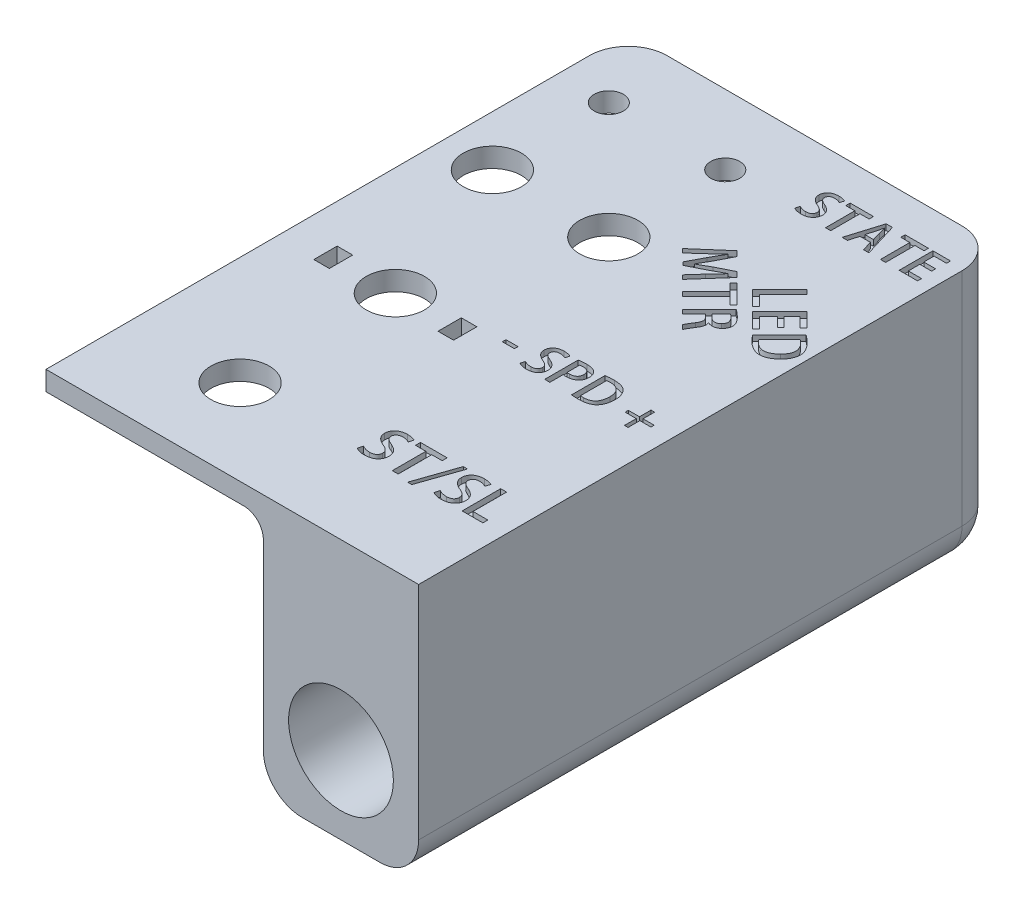
SolidWorks part; units mm, degrees
ref_plane "Front Plane" through (0, 0, 0) normal (0, 0, 1) x (1, 0, 0)
ref_plane "Top Plane" through (0, 0, 0) normal (0, 1, 0) x (1, 0, 0)
ref_plane "Right Plane" through (0, 0, 0) normal (1, 0, 0) x (0, 0, -1)
sketch "Sketch1" plane through (0, 0, 0) normal (0, 1, 0) x (1, 0, 0)
  line L0 (28, 75) -> (28, 0) construction
  line L1 (0, 0) -> (48, 0)
  line L2 (0, 0) -> (0, 70)
  line L3 (5, 75) -> (43, 75)
  line L4 (48, 0) -> (48, 70)
  line L5 (6.5, 51) -> (21.5, 51) construction
  line L6 (5, 32.5) -> (7, 32.5)
  line L7 (5, 32.5) -> (5, 29.5)
  line L8 (5, 29.5) -> (7, 29.5)
  line L9 (7, 32.5) -> (7, 29.5)
  line L10 (23, 32.5) -> (21, 32.5)
  line L11 (23, 32.5) -> (23, 29.5)
  line L12 (23, 29.5) -> (21, 29.5)
  line L13 (21, 32.5) -> (21, 29.5)
  line L14 (6.5, 66) -> (21.5, 66) construction
  circle A0 centre (14, 11) radius 3.75
  circle A1 centre (14, 31) radius 3.75
  circle A2 centre (6.5, 51) radius 3.75
  circle A3 centre (21.5, 51) radius 3.75
  circle A4 centre (6.5, 66) radius 1.875
  circle A5 centre (21.5, 66) radius 1.875
  arc A6 (48, 70) -> (43, 75) centre (43, 70) ccw
  arc A7 (5, 75) -> (0, 70) centre (5, 70) ccw
  point P27 (6, 32.5)
  point P28 (22, 32.5)
  point P29 (21, 31)
  point P30 (5, 31)
  point P31 (14, 51)
  point P32 (0, 0)
  point P33 (14, 66)
  point P36 (48, 75)
  point P39 (0, 75)
  dimension "D4" = 7.5
  dimension "D8" = 20
  dimension "D15" = 5
  dimension "D16" = 3.75
  dimension "D1" = 75
  dimension "D2" = 48
  dimension "D3" = 20
  dimension "D5" = 11
  dimension "D6" = 20
  dimension "D7" = 14
  dimension "D9" = 8
  dimension "D10" = 8
  dimension "D11" = 2
  dimension "D12" = 3
  dimension "D13" = 15
  dimension "D14" = 15
extrude "Boss-Extrude1" add sketch "Sketch1" along normal blind 2.5
sketch "Sketch2" plane through (0, 0, 0) normal (0, -1, 0) x (1, 0, 0)
  line L0 (43, -75) -> (5, -75) construction
  line L1 (48, 0) -> (28, 0)
  line L2 (48, 0) -> (48, -70)
  line L3 (43, -75) -> (28, -75)
  line L4 (28, 0) -> (28, -75)
  arc A0 (48, -70) -> (43, -75) centre (43, -70) cw
  dimension "D2" = 5
  dimension "D1" = 20
extrude "Boss-Extrude2" add sketch "Sketch2" along normal blind 31
sketch "Sketch3" plane through (0, 0, 0) normal (0, 0, 1) x (1, 0, 0)
  line L0 (28, -11) -> (48, -11) construction
  line L1 (28, -31) -> (28, 0) construction
  line L2 (48, 2.5) -> (48, -31) construction
  line L3 (48, -31) -> (28, -31) construction
  circle A0 centre (38, -21) radius 6.75
  point P10 (38, -11)
  dimension "D3" = 13.5
  dimension "D1" = 20
  dimension "D2" = 10
extrude "Cut-Extrude1" cut sketch "Sketch3" against normal blind 84
sketch "Sketch4" plane through (0, 0, 0) normal (0, 0, 1) x (1, 0, 0)
  line L0 (0, 0) -> (28, 0) construction
  line L1 (28, -31) -> (28, 0) construction
  line L2 (28, 0) -> (25.5, 0)
  line L3 (28, 0) -> (28, -2.5)
  circle A0 centre (25.5, -2.5) radius 2.5
  line M3 (0, 0) -> (28, 0)
  line M4 (28, 0) -> (28, -31)
  dimension "D1" = 5
extrude "Boss-Extrude3" add sketch "Sketch4" against normal blind 40 contours A0 M4 M3 region at (27.4416, -0.5584, 0)
sketch "Sketch5" plane through (0, 0, -75) normal (0, 0, -1) x (-1, 0, 0)
  line L0 (-28, 0) -> (-5, 0) construction
  line L1 (-28, -31) -> (-28, 0) construction
  line L2 (-28, 0) -> (-25.5, 0)
  line L3 (-28, 0) -> (-28, -2.5)
  circle A0 centre (-25.5, -2.5) radius 2.5
  line M6 (-28, -31) -> (-28, 0)
  line M7 (-28, 0) -> (-5, 0)
  dimension "D1" = 5
extrude "Boss-Extrude4" add sketch "Sketch5" against normal blind 10 contours A0 M7 M6 region at (27.4416, -0.5584, -75)
fillet "Fillet1" radius 5 4 edges at (35.5, -31, -75) (46.5355, -31, -73.5355) (48, -31, -35) (28, -31, -37.5)
sketch "Sketch6" plane through (0, 2.5, 0) normal (0, 1, 0) x (1, 0, 0)
  line L0 (21.5, 54.75) -> (48, 54.75) construction
  line L1 (48, 0) -> (48, 70) construction
  line L2 (21.5, 47.25) -> (48, 47.25) construction
  line L3 (27.25, 54.75) -> (34.75, 47.25) construction
  line L4 (36.25, 54.75) -> (43.75, 47.25) construction
  line L5 (14, 31) -> (48, 31) construction
  line L6 (14, 11) -> (48, 11) construction
  line L7 (28, 0) -> (28, 75) construction
  line L8 (0, 0) -> (48, 0) construction
  line L9 (43, 75) -> (5, 75) construction
  line L10 (0, 57) -> (48, 57) construction
  line L11 (0, 70) -> (0, 0) construction
  line L12 (0, 40) -> (48, 40) construction
  line L13 (6.5, 51) -> (0, 51) construction
  line L14 (21.5, 66) -> (48, 66) construction
  circle A0 centre (21.5, 51) radius 3.75 construction
  text T0 "MTR" font "Kozuka Gothic Pr6N M" height in points 16
  text T1 "LED" font "Kozuka Gothic Pr6N M" height in points 16
  text T2 "       - SPD +" font "Kozuka Gothic Pr6N M" height in points 14
  text T3 "         ST/SL" font "Kozuka Gothic Pr6N M" height in points 16
  text T4 "      STATE" font "Kozuka Gothic Pr6N M" height in points 14
  dimension "D1" = 7.5
  dimension "D2" = 45
  dimension "D3" = 9
  dimension "D4" = 20
  dimension "D5" = 17
  dimension "D6" = 6
extrude "Cut-Extrude2" cut sketch "Sketch6" against normal blind 0.75
